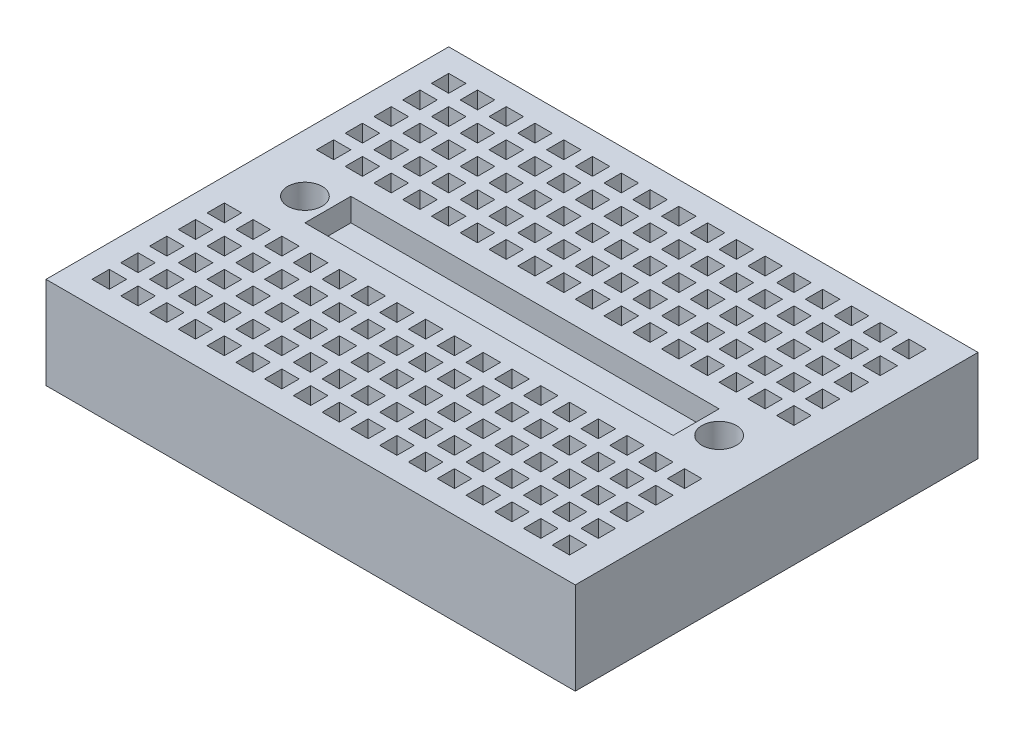
SolidWorks part; units mm, degrees
ref_plane "Front Plane" through (0, 0, 0) normal (0, 0, 1) x (1, 0, 0)
ref_plane "Top Plane" through (0, 0, 0) normal (0, 1, 0) x (1, 0, 0)
ref_plane "Right Plane" through (0, 0, 0) normal (1, 0, 0) x (0, 0, -1)
sketch "Sketch1" plane through (0, 0, 0) normal (0, 1, 0) x (1, 0, 0)
  line L1 (23, -17.5) -> (-23, -17.5)
  line L2 (23, -17.5) -> (23, 17.5)
  line L3 (23, 17.5) -> (-23, 17.5)
  line L4 (-23, -17.5) -> (-23, 17.5)
  line L5 (23, -17.5) -> (-23, 17.5) construction
  line L6 (23, 17.5) -> (-23, -17.5) construction
  circle A0 centre (18, 0) radius 1.5
  circle A1 centre (-18, 0) radius 1.5
  point P0 (0, 0)
  point P11 (-18, 0)
  dimension "D3" = 3
  dimension "D4" = 3
  dimension "D1" = 46
  dimension "D2" = 35
  dimension "D5" = 5
  dimension "D6" = 5
extrude "Boss-Extrude1" add sketch "Sketch1" along normal blind 8
sketch "Sketch3" plane through (0, 8, 0) normal (0, 1, 0) x (1, 0, 0)
  line L0 (23, 17.5) -> (-23, 17.5) construction
  line L1 (-21, 15.5) -> (-19.5, 15.5)
  line L2 (-21, 15.5) -> (-21, 14)
  line L3 (-21, 14) -> (-19.5, 14)
  line L4 (-19.5, 15.5) -> (-19.5, 14)
  line L5 (-21, 15.5) -> (-19.5, 14) construction
  line L6 (-21, 14) -> (-19.5, 15.5) construction
  line L7 (-23, 17.5) -> (-23, -17.5) construction
  line L8 (-18.5, 15.5) -> (-17, 15.5)
  line L9 (-18.5, 15.5) -> (-18.5, 14)
  line L10 (-17, 15.5) -> (-17, 14)
  line L11 (-18.5, 14) -> (-17, 14)
  line L12 (-16, 15.5) -> (-14.5, 15.5)
  line L13 (-16, 15.5) -> (-16, 14)
  line L14 (-14.5, 15.5) -> (-14.5, 14)
  line L15 (-16, 14) -> (-14.5, 14)
  line L16 (-13.5, 15.5) -> (-12, 15.5)
  line L17 (-13.5, 15.5) -> (-13.5, 14)
  line L18 (-12, 15.5) -> (-12, 14)
  line L19 (-13.5, 14) -> (-12, 14)
  line L20 (-11, 15.5) -> (-9.5, 15.5)
  line L21 (-11, 15.5) -> (-11, 14)
  line L22 (-9.5, 15.5) -> (-9.5, 14)
  line L23 (-11, 14) -> (-9.5, 14)
  line L24 (-8.5, 15.5) -> (-7, 15.5)
  line L25 (-8.5, 15.5) -> (-8.5, 14)
  line L26 (-7, 15.5) -> (-7, 14)
  line L27 (-8.5, 14) -> (-7, 14)
  line L28 (-6, 15.5) -> (-4.5, 15.5)
  line L29 (-6, 15.5) -> (-6, 14)
  line L30 (-4.5, 15.5) -> (-4.5, 14)
  line L31 (-6, 14) -> (-4.5, 14)
  line L32 (-3.5, 15.5) -> (-2, 15.5)
  line L33 (-3.5, 15.5) -> (-3.5, 14)
  line L34 (-2, 15.5) -> (-2, 14)
  line L35 (-3.5, 14) -> (-2, 14)
  line L36 (-1, 15.5) -> (0.5, 15.5)
  line L37 (-1, 15.5) -> (-1, 14)
  line L38 (0.5, 15.5) -> (0.5, 14)
  line L39 (-1, 14) -> (0.5, 14)
  line L40 (1.5, 15.5) -> (3, 15.5)
  line L41 (1.5, 15.5) -> (1.5, 14)
  line L42 (3, 15.5) -> (3, 14)
  line L43 (1.5, 14) -> (3, 14)
  line L44 (4, 15.5) -> (5.5, 15.5)
  line L45 (4, 15.5) -> (4, 14)
  line L46 (5.5, 15.5) -> (5.5, 14)
  line L47 (4, 14) -> (5.5, 14)
  line L48 (6.5, 15.5) -> (8, 15.5)
  line L49 (6.5, 15.5) -> (6.5, 14)
  line L50 (8, 15.5) -> (8, 14)
  line L51 (6.5, 14) -> (8, 14)
  line L52 (9, 15.5) -> (10.5, 15.5)
  line L53 (9, 15.5) -> (9, 14)
  line L54 (10.5, 15.5) -> (10.5, 14)
  line L55 (9, 14) -> (10.5, 14)
  line L56 (11.5, 15.5) -> (13, 15.5)
  line L57 (11.5, 15.5) -> (11.5, 14)
  line L58 (13, 15.5) -> (13, 14)
  line L59 (11.5, 14) -> (13, 14)
  line L60 (14, 15.5) -> (15.5, 15.5)
  line L61 (14, 15.5) -> (14, 14)
  line L62 (15.5, 15.5) -> (15.5, 14)
  line L63 (14, 14) -> (15.5, 14)
  line L64 (16.5, 15.5) -> (18, 15.5)
  line L65 (16.5, 15.5) -> (16.5, 14)
  line L66 (18, 15.5) -> (18, 14)
  line L67 (16.5, 14) -> (18, 14)
  line L68 (19, 15.5) -> (20.5, 15.5)
  line L69 (19, 15.5) -> (19, 14)
  line L70 (20.5, 15.5) -> (20.5, 14)
  line L71 (19, 14) -> (20.5, 14)
  line L72 (-18.5, 13) -> (-17, 13)
  line L73 (-18.5, 13) -> (-18.5, 11.5)
  line L74 (-17, 13) -> (-17, 11.5)
  line L75 (-18.5, 11.5) -> (-17, 11.5)
  line L76 (-16, 13) -> (-14.5, 13)
  line L77 (-16, 13) -> (-16, 11.5)
  line L78 (-14.5, 13) -> (-14.5, 11.5)
  line L79 (-16, 11.5) -> (-14.5, 11.5)
  line L80 (-13.5, 13) -> (-12, 13)
  line L81 (-13.5, 13) -> (-13.5, 11.5)
  line L82 (-12, 13) -> (-12, 11.5)
  line L83 (-13.5, 11.5) -> (-12, 11.5)
  line L84 (-11, 13) -> (-9.5, 13)
  line L85 (-11, 13) -> (-11, 11.5)
  line L86 (-9.5, 13) -> (-9.5, 11.5)
  line L87 (-11, 11.5) -> (-9.5, 11.5)
  line L88 (-8.5, 13) -> (-7, 13)
  line L89 (-8.5, 13) -> (-8.5, 11.5)
  line L90 (-7, 13) -> (-7, 11.5)
  line L91 (-8.5, 11.5) -> (-7, 11.5)
  line L92 (-6, 13) -> (-4.5, 13)
  line L93 (-6, 13) -> (-6, 11.5)
  line L94 (-4.5, 13) -> (-4.5, 11.5)
  line L95 (-6, 11.5) -> (-4.5, 11.5)
  line L96 (-3.5, 13) -> (-2, 13)
  line L97 (-3.5, 13) -> (-3.5, 11.5)
  line L98 (-2, 13) -> (-2, 11.5)
  line L99 (-3.5, 11.5) -> (-2, 11.5)
  line L100 (-1, 13) -> (0.5, 13)
  line L101 (-1, 13) -> (-1, 11.5)
  line L102 (0.5, 13) -> (0.5, 11.5)
  line L103 (-1, 11.5) -> (0.5, 11.5)
  line L104 (1.5, 13) -> (3, 13)
  line L105 (1.5, 13) -> (1.5, 11.5)
  line L106 (3, 13) -> (3, 11.5)
  line L107 (1.5, 11.5) -> (3, 11.5)
  line L108 (4, 13) -> (5.5, 13)
  line L109 (4, 13) -> (4, 11.5)
  line L110 (5.5, 13) -> (5.5, 11.5)
  line L111 (4, 11.5) -> (5.5, 11.5)
  line L112 (6.5, 13) -> (8, 13)
  line L113 (6.5, 13) -> (6.5, 11.5)
  line L114 (8, 13) -> (8, 11.5)
  line L115 (6.5, 11.5) -> (8, 11.5)
  line L116 (9, 13) -> (10.5, 13)
  line L117 (9, 13) -> (9, 11.5)
  line L118 (10.5, 13) -> (10.5, 11.5)
  line L119 (9, 11.5) -> (10.5, 11.5)
  line L120 (11.5, 13) -> (13, 13)
  line L121 (11.5, 13) -> (11.5, 11.5)
  line L122 (13, 13) -> (13, 11.5)
  line L123 (11.5, 11.5) -> (13, 11.5)
  line L124 (14, 13) -> (15.5, 13)
  line L125 (14, 13) -> (14, 11.5)
  line L126 (15.5, 13) -> (15.5, 11.5)
  line L127 (14, 11.5) -> (15.5, 11.5)
  line L128 (16.5, 13) -> (18, 13)
  line L129 (16.5, 13) -> (16.5, 11.5)
  line L130 (18, 13) -> (18, 11.5)
  line L131 (16.5, 11.5) -> (18, 11.5)
  line L132 (19, 13) -> (20.5, 13)
  line L133 (19, 13) -> (19, 11.5)
  line L134 (20.5, 13) -> (20.5, 11.5)
  line L135 (19, 11.5) -> (20.5, 11.5)
  line L136 (-18.5, 10.5) -> (-17, 10.5)
  line L137 (-18.5, 10.5) -> (-18.5, 9)
  line L138 (-17, 10.5) -> (-17, 9)
  line L139 (-18.5, 9) -> (-17, 9)
  line L140 (-16, 10.5) -> (-14.5, 10.5)
  line L141 (-16, 10.5) -> (-16, 9)
  line L142 (-14.5, 10.5) -> (-14.5, 9)
  line L143 (-16, 9) -> (-14.5, 9)
  line L144 (-13.5, 10.5) -> (-12, 10.5)
  line L145 (-13.5, 10.5) -> (-13.5, 9)
  line L146 (-12, 10.5) -> (-12, 9)
  line L147 (-13.5, 9) -> (-12, 9)
  line L148 (-11, 10.5) -> (-9.5, 10.5)
  line L149 (-11, 10.5) -> (-11, 9)
  line L150 (-9.5, 10.5) -> (-9.5, 9)
  line L151 (-11, 9) -> (-9.5, 9)
  line L152 (-8.5, 10.5) -> (-7, 10.5)
  line L153 (-8.5, 10.5) -> (-8.5, 9)
  line L154 (-7, 10.5) -> (-7, 9)
  line L155 (-8.5, 9) -> (-7, 9)
  line L156 (-6, 10.5) -> (-4.5, 10.5)
  line L157 (-6, 10.5) -> (-6, 9)
  line L158 (-4.5, 10.5) -> (-4.5, 9)
  line L159 (-6, 9) -> (-4.5, 9)
  line L160 (-3.5, 10.5) -> (-2, 10.5)
  line L161 (-3.5, 10.5) -> (-3.5, 9)
  line L162 (-2, 10.5) -> (-2, 9)
  line L163 (-3.5, 9) -> (-2, 9)
  line L164 (-1, 10.5) -> (0.5, 10.5)
  line L165 (-1, 10.5) -> (-1, 9)
  line L166 (0.5, 10.5) -> (0.5, 9)
  line L167 (-1, 9) -> (0.5, 9)
  line L168 (1.5, 10.5) -> (3, 10.5)
  line L169 (1.5, 10.5) -> (1.5, 9)
  line L170 (3, 10.5) -> (3, 9)
  line L171 (1.5, 9) -> (3, 9)
  line L172 (4, 10.5) -> (5.5, 10.5)
  line L173 (4, 10.5) -> (4, 9)
  line L174 (5.5, 10.5) -> (5.5, 9)
  line L175 (4, 9) -> (5.5, 9)
  line L176 (6.5, 10.5) -> (8, 10.5)
  line L177 (6.5, 10.5) -> (6.5, 9)
  line L178 (8, 10.5) -> (8, 9)
  line L179 (6.5, 9) -> (8, 9)
  line L180 (9, 10.5) -> (10.5, 10.5)
  line L181 (9, 10.5) -> (9, 9)
  line L182 (10.5, 10.5) -> (10.5, 9)
  line L183 (9, 9) -> (10.5, 9)
  line L184 (11.5, 10.5) -> (13, 10.5)
  line L185 (11.5, 10.5) -> (11.5, 9)
  line L186 (13, 10.5) -> (13, 9)
  line L187 (11.5, 9) -> (13, 9)
  line L188 (14, 10.5) -> (15.5, 10.5)
  line L189 (14, 10.5) -> (14, 9)
  line L190 (15.5, 10.5) -> (15.5, 9)
  line L191 (14, 9) -> (15.5, 9)
  line L192 (16.5, 10.5) -> (18, 10.5)
  line L193 (16.5, 10.5) -> (16.5, 9)
  line L194 (18, 10.5) -> (18, 9)
  line L195 (16.5, 9) -> (18, 9)
  line L196 (19, 10.5) -> (20.5, 10.5)
  line L197 (19, 10.5) -> (19, 9)
  line L198 (20.5, 10.5) -> (20.5, 9)
  line L199 (19, 9) -> (20.5, 9)
  line L200 (-18.5, 8) -> (-17, 8)
  line L201 (-18.5, 8) -> (-18.5, 6.5)
  line L202 (-17, 8) -> (-17, 6.5)
  line L203 (-18.5, 6.5) -> (-17, 6.5)
  line L204 (-16, 8) -> (-14.5, 8)
  line L205 (-16, 8) -> (-16, 6.5)
  line L206 (-14.5, 8) -> (-14.5, 6.5)
  line L207 (-16, 6.5) -> (-14.5, 6.5)
  line L208 (-13.5, 8) -> (-12, 8)
  line L209 (-13.5, 8) -> (-13.5, 6.5)
  line L210 (-12, 8) -> (-12, 6.5)
  line L211 (-13.5, 6.5) -> (-12, 6.5)
  line L212 (-11, 8) -> (-9.5, 8)
  line L213 (-11, 8) -> (-11, 6.5)
  line L214 (-9.5, 8) -> (-9.5, 6.5)
  line L215 (-11, 6.5) -> (-9.5, 6.5)
  line L216 (-8.5, 8) -> (-7, 8)
  line L217 (-8.5, 8) -> (-8.5, 6.5)
  line L218 (-7, 8) -> (-7, 6.5)
  line L219 (-8.5, 6.5) -> (-7, 6.5)
  line L220 (-6, 8) -> (-4.5, 8)
  line L221 (-6, 8) -> (-6, 6.5)
  line L222 (-4.5, 8) -> (-4.5, 6.5)
  line L223 (-6, 6.5) -> (-4.5, 6.5)
  line L224 (-3.5, 8) -> (-2, 8)
  line L225 (-3.5, 8) -> (-3.5, 6.5)
  line L226 (-2, 8) -> (-2, 6.5)
  line L227 (-3.5, 6.5) -> (-2, 6.5)
  line L228 (-1, 8) -> (0.5, 8)
  line L229 (-1, 8) -> (-1, 6.5)
  line L230 (0.5, 8) -> (0.5, 6.5)
  line L231 (-1, 6.5) -> (0.5, 6.5)
  line L232 (1.5, 8) -> (3, 8)
  line L233 (1.5, 8) -> (1.5, 6.5)
  line L234 (3, 8) -> (3, 6.5)
  line L235 (1.5, 6.5) -> (3, 6.5)
  line L236 (4, 8) -> (5.5, 8)
  line L237 (4, 8) -> (4, 6.5)
  line L238 (5.5, 8) -> (5.5, 6.5)
  line L239 (4, 6.5) -> (5.5, 6.5)
  line L240 (6.5, 8) -> (8, 8)
  line L241 (6.5, 8) -> (6.5, 6.5)
  line L242 (8, 8) -> (8, 6.5)
  line L243 (6.5, 6.5) -> (8, 6.5)
  line L244 (9, 8) -> (10.5, 8)
  line L245 (9, 8) -> (9, 6.5)
  line L246 (10.5, 8) -> (10.5, 6.5)
  line L247 (9, 6.5) -> (10.5, 6.5)
  line L248 (11.5, 8) -> (13, 8)
  line L249 (11.5, 8) -> (11.5, 6.5)
  line L250 (13, 8) -> (13, 6.5)
  line L251 (11.5, 6.5) -> (13, 6.5)
  line L252 (14, 8) -> (15.5, 8)
  line L253 (14, 8) -> (14, 6.5)
  line L254 (15.5, 8) -> (15.5, 6.5)
  line L255 (14, 6.5) -> (15.5, 6.5)
  line L256 (16.5, 8) -> (18, 8)
  line L257 (16.5, 8) -> (16.5, 6.5)
  line L258 (18, 8) -> (18, 6.5)
  line L259 (16.5, 6.5) -> (18, 6.5)
  line L260 (19, 8) -> (20.5, 8)
  line L261 (19, 8) -> (19, 6.5)
  line L262 (20.5, 8) -> (20.5, 6.5)
  line L263 (19, 6.5) -> (20.5, 6.5)
  line L264 (-18.5, 5.5) -> (-17, 5.5)
  line L265 (-18.5, 5.5) -> (-18.5, 4)
  line L266 (-17, 5.5) -> (-17, 4)
  line L267 (-18.5, 4) -> (-17, 4)
  line L268 (-16, 5.5) -> (-14.5, 5.5)
  line L269 (-16, 5.5) -> (-16, 4)
  line L270 (-14.5, 5.5) -> (-14.5, 4)
  line L271 (-16, 4) -> (-14.5, 4)
  line L272 (-13.5, 5.5) -> (-12, 5.5)
  line L273 (-13.5, 5.5) -> (-13.5, 4)
  line L274 (-12, 5.5) -> (-12, 4)
  line L275 (-13.5, 4) -> (-12, 4)
  line L276 (-11, 5.5) -> (-9.5, 5.5)
  line L277 (-11, 5.5) -> (-11, 4)
  line L278 (-9.5, 5.5) -> (-9.5, 4)
  line L279 (-11, 4) -> (-9.5, 4)
  line L280 (-8.5, 5.5) -> (-7, 5.5)
  line L281 (-8.5, 5.5) -> (-8.5, 4)
  line L282 (-7, 5.5) -> (-7, 4)
  line L283 (-8.5, 4) -> (-7, 4)
  line L284 (-6, 5.5) -> (-4.5, 5.5)
  line L285 (-6, 5.5) -> (-6, 4)
  line L286 (-4.5, 5.5) -> (-4.5, 4)
  line L287 (-6, 4) -> (-4.5, 4)
  line L288 (-3.5, 5.5) -> (-2, 5.5)
  line L289 (-3.5, 5.5) -> (-3.5, 4)
  line L290 (-2, 5.5) -> (-2, 4)
  line L291 (-3.5, 4) -> (-2, 4)
  line L292 (-1, 5.5) -> (0.5, 5.5)
  line L293 (-1, 5.5) -> (-1, 4)
  line L294 (0.5, 5.5) -> (0.5, 4)
  line L295 (-1, 4) -> (0.5, 4)
  line L296 (1.5, 5.5) -> (3, 5.5)
  line L297 (1.5, 5.5) -> (1.5, 4)
  line L298 (3, 5.5) -> (3, 4)
  line L299 (1.5, 4) -> (3, 4)
  line L300 (4, 5.5) -> (5.5, 5.5)
  line L301 (4, 5.5) -> (4, 4)
  line L302 (5.5, 5.5) -> (5.5, 4)
  line L303 (4, 4) -> (5.5, 4)
  line L304 (6.5, 5.5) -> (8, 5.5)
  line L305 (6.5, 5.5) -> (6.5, 4)
  line L306 (8, 5.5) -> (8, 4)
  line L307 (6.5, 4) -> (8, 4)
  line L308 (9, 5.5) -> (10.5, 5.5)
  line L309 (9, 5.5) -> (9, 4)
  line L310 (10.5, 5.5) -> (10.5, 4)
  line L311 (9, 4) -> (10.5, 4)
  line L312 (11.5, 5.5) -> (13, 5.5)
  line L313 (11.5, 5.5) -> (11.5, 4)
  line L314 (13, 5.5) -> (13, 4)
  line L315 (11.5, 4) -> (13, 4)
  line L316 (14, 5.5) -> (15.5, 5.5)
  line L317 (14, 5.5) -> (14, 4)
  line L318 (15.5, 5.5) -> (15.5, 4)
  line L319 (14, 4) -> (15.5, 4)
  line L320 (16.5, 5.5) -> (18, 5.5)
  line L321 (16.5, 5.5) -> (16.5, 4)
  line L322 (18, 5.5) -> (18, 4)
  line L323 (16.5, 4) -> (18, 4)
  line L324 (19, 5.5) -> (20.5, 5.5)
  line L325 (19, 5.5) -> (19, 4)
  line L326 (20.5, 5.5) -> (20.5, 4)
  line L327 (19, 4) -> (20.5, 4)
  line L328 (-21, 13) -> (-19.5, 13)
  line L329 (-21, 13) -> (-21, 11.5)
  line L330 (-19.5, 13) -> (-19.5, 11.5)
  line L331 (-21, 11.5) -> (-19.5, 11.5)
  line L332 (-21, 10.5) -> (-19.5, 10.5)
  line L333 (-21, 10.5) -> (-21, 9)
  line L334 (-19.5, 10.5) -> (-19.5, 9)
  line L335 (-21, 9) -> (-19.5, 9)
  line L336 (-21, 8) -> (-19.5, 8)
  line L337 (-21, 8) -> (-21, 6.5)
  line L338 (-19.5, 8) -> (-19.5, 6.5)
  line L339 (-21, 6.5) -> (-19.5, 6.5)
  line L340 (-21, 5.5) -> (-19.5, 5.5)
  line L341 (-21, 5.5) -> (-21, 4)
  line L342 (-19.5, 5.5) -> (-19.5, 4)
  line L343 (-21, 4) -> (-19.5, 4)
  line L344 (-23, 0) -> (23, 0) construction
  line L345 (23, -17.5) -> (23, 17.5) construction
  line L346 (-21, -14) -> (-19.5, -15.5) construction
  line L347 (-21, -15.5) -> (-19.5, -14) construction
  line L348 (-21, -4) -> (-19.5, -4)
  line L349 (-19.5, -5.5) -> (-19.5, -4)
  line L350 (-21, -5.5) -> (-21, -4)
  line L351 (-21, -5.5) -> (-19.5, -5.5)
  line L352 (-21, -6.5) -> (-19.5, -6.5)
  line L353 (-19.5, -8) -> (-19.5, -6.5)
  line L354 (-21, -8) -> (-21, -6.5)
  line L355 (-21, -8) -> (-19.5, -8)
  line L356 (-21, -9) -> (-19.5, -9)
  line L357 (-19.5, -10.5) -> (-19.5, -9)
  line L358 (-21, -10.5) -> (-21, -9)
  line L359 (-21, -10.5) -> (-19.5, -10.5)
  line L360 (-21, -11.5) -> (-19.5, -11.5)
  line L361 (-19.5, -13) -> (-19.5, -11.5)
  line L362 (-21, -13) -> (-21, -11.5)
  line L363 (-21, -13) -> (-19.5, -13)
  line L364 (19, -4) -> (20.5, -4)
  line L365 (20.5, -5.5) -> (20.5, -4)
  line L366 (19, -5.5) -> (19, -4)
  line L367 (19, -5.5) -> (20.5, -5.5)
  line L368 (16.5, -4) -> (18, -4)
  line L369 (18, -5.5) -> (18, -4)
  line L370 (16.5, -5.5) -> (16.5, -4)
  line L371 (16.5, -5.5) -> (18, -5.5)
  line L372 (14, -4) -> (15.5, -4)
  line L373 (15.5, -5.5) -> (15.5, -4)
  line L374 (14, -5.5) -> (14, -4)
  line L375 (14, -5.5) -> (15.5, -5.5)
  line L376 (11.5, -4) -> (13, -4)
  line L377 (13, -5.5) -> (13, -4)
  line L378 (11.5, -5.5) -> (11.5, -4)
  line L379 (11.5, -5.5) -> (13, -5.5)
  line L380 (9, -4) -> (10.5, -4)
  line L381 (10.5, -5.5) -> (10.5, -4)
  line L382 (9, -5.5) -> (9, -4)
  line L383 (9, -5.5) -> (10.5, -5.5)
  line L384 (6.5, -4) -> (8, -4)
  line L385 (8, -5.5) -> (8, -4)
  line L386 (6.5, -5.5) -> (6.5, -4)
  line L387 (6.5, -5.5) -> (8, -5.5)
  line L388 (4, -4) -> (5.5, -4)
  line L389 (5.5, -5.5) -> (5.5, -4)
  line L390 (4, -5.5) -> (4, -4)
  line L391 (4, -5.5) -> (5.5, -5.5)
  line L392 (1.5, -4) -> (3, -4)
  line L393 (3, -5.5) -> (3, -4)
  line L394 (1.5, -5.5) -> (1.5, -4)
  line L395 (1.5, -5.5) -> (3, -5.5)
  line L396 (-1, -4) -> (0.5, -4)
  line L397 (0.5, -5.5) -> (0.5, -4)
  line L398 (-1, -5.5) -> (-1, -4)
  line L399 (-1, -5.5) -> (0.5, -5.5)
  line L400 (-3.5, -4) -> (-2, -4)
  line L401 (-2, -5.5) -> (-2, -4)
  line L402 (-3.5, -5.5) -> (-3.5, -4)
  line L403 (-3.5, -5.5) -> (-2, -5.5)
  line L404 (-6, -4) -> (-4.5, -4)
  line L405 (-4.5, -5.5) -> (-4.5, -4)
  line L406 (-6, -5.5) -> (-6, -4)
  line L407 (-6, -5.5) -> (-4.5, -5.5)
  line L408 (-8.5, -4) -> (-7, -4)
  line L409 (-7, -5.5) -> (-7, -4)
  line L410 (-8.5, -5.5) -> (-8.5, -4)
  line L411 (-8.5, -5.5) -> (-7, -5.5)
  line L412 (-11, -4) -> (-9.5, -4)
  line L413 (-9.5, -5.5) -> (-9.5, -4)
  line L414 (-11, -5.5) -> (-11, -4)
  line L415 (-11, -5.5) -> (-9.5, -5.5)
  line L416 (-13.5, -4) -> (-12, -4)
  line L417 (-12, -5.5) -> (-12, -4)
  line L418 (-13.5, -5.5) -> (-13.5, -4)
  line L419 (-13.5, -5.5) -> (-12, -5.5)
  line L420 (-16, -4) -> (-14.5, -4)
  line L421 (-14.5, -5.5) -> (-14.5, -4)
  line L422 (-16, -5.5) -> (-16, -4)
  line L423 (-16, -5.5) -> (-14.5, -5.5)
  line L424 (-18.5, -4) -> (-17, -4)
  line L425 (-17, -5.5) -> (-17, -4)
  line L426 (-18.5, -5.5) -> (-18.5, -4)
  line L427 (-18.5, -5.5) -> (-17, -5.5)
  line L428 (19, -6.5) -> (20.5, -6.5)
  line L429 (20.5, -8) -> (20.5, -6.5)
  line L430 (19, -8) -> (19, -6.5)
  line L431 (19, -8) -> (20.5, -8)
  line L432 (16.5, -6.5) -> (18, -6.5)
  line L433 (18, -8) -> (18, -6.5)
  line L434 (16.5, -8) -> (16.5, -6.5)
  line L435 (16.5, -8) -> (18, -8)
  line L436 (14, -6.5) -> (15.5, -6.5)
  line L437 (15.5, -8) -> (15.5, -6.5)
  line L438 (14, -8) -> (14, -6.5)
  line L439 (14, -8) -> (15.5, -8)
  line L440 (11.5, -6.5) -> (13, -6.5)
  line L441 (13, -8) -> (13, -6.5)
  line L442 (11.5, -8) -> (11.5, -6.5)
  line L443 (11.5, -8) -> (13, -8)
  line L444 (9, -6.5) -> (10.5, -6.5)
  line L445 (10.5, -8) -> (10.5, -6.5)
  line L446 (9, -8) -> (9, -6.5)
  line L447 (9, -8) -> (10.5, -8)
  line L448 (6.5, -6.5) -> (8, -6.5)
  line L449 (8, -8) -> (8, -6.5)
  line L450 (6.5, -8) -> (6.5, -6.5)
  line L451 (6.5, -8) -> (8, -8)
  line L452 (4, -6.5) -> (5.5, -6.5)
  line L453 (5.5, -8) -> (5.5, -6.5)
  line L454 (4, -8) -> (4, -6.5)
  line L455 (4, -8) -> (5.5, -8)
  line L456 (1.5, -6.5) -> (3, -6.5)
  line L457 (3, -8) -> (3, -6.5)
  line L458 (1.5, -8) -> (1.5, -6.5)
  line L459 (1.5, -8) -> (3, -8)
  line L460 (-1, -6.5) -> (0.5, -6.5)
  line L461 (0.5, -8) -> (0.5, -6.5)
  line L462 (-1, -8) -> (-1, -6.5)
  line L463 (-1, -8) -> (0.5, -8)
  line L464 (-3.5, -6.5) -> (-2, -6.5)
  line L465 (-2, -8) -> (-2, -6.5)
  line L466 (-3.5, -8) -> (-3.5, -6.5)
  line L467 (-3.5, -8) -> (-2, -8)
  line L468 (-6, -6.5) -> (-4.5, -6.5)
  line L469 (-4.5, -8) -> (-4.5, -6.5)
  line L470 (-6, -8) -> (-6, -6.5)
  line L471 (-6, -8) -> (-4.5, -8)
  line L472 (-8.5, -6.5) -> (-7, -6.5)
  line L473 (-7, -8) -> (-7, -6.5)
  line L474 (-8.5, -8) -> (-8.5, -6.5)
  line L475 (-8.5, -8) -> (-7, -8)
  line L476 (-11, -6.5) -> (-9.5, -6.5)
  line L477 (-9.5, -8) -> (-9.5, -6.5)
  line L478 (-11, -8) -> (-11, -6.5)
  line L479 (-11, -8) -> (-9.5, -8)
  line L480 (-13.5, -6.5) -> (-12, -6.5)
  line L481 (-12, -8) -> (-12, -6.5)
  line L482 (-13.5, -8) -> (-13.5, -6.5)
  line L483 (-13.5, -8) -> (-12, -8)
  line L484 (-16, -6.5) -> (-14.5, -6.5)
  line L485 (-14.5, -8) -> (-14.5, -6.5)
  line L486 (-16, -8) -> (-16, -6.5)
  line L487 (-16, -8) -> (-14.5, -8)
  line L488 (-18.5, -6.5) -> (-17, -6.5)
  line L489 (-17, -8) -> (-17, -6.5)
  line L490 (-18.5, -8) -> (-18.5, -6.5)
  line L491 (-18.5, -8) -> (-17, -8)
  line L492 (19, -9) -> (20.5, -9)
  line L493 (20.5, -10.5) -> (20.5, -9)
  line L494 (19, -10.5) -> (19, -9)
  line L495 (19, -10.5) -> (20.5, -10.5)
  line L496 (16.5, -9) -> (18, -9)
  line L497 (18, -10.5) -> (18, -9)
  line L498 (16.5, -10.5) -> (16.5, -9)
  line L499 (16.5, -10.5) -> (18, -10.5)
  line L500 (14, -9) -> (15.5, -9)
  line L501 (15.5, -10.5) -> (15.5, -9)
  line L502 (14, -10.5) -> (14, -9)
  line L503 (14, -10.5) -> (15.5, -10.5)
  line L504 (11.5, -9) -> (13, -9)
  line L505 (13, -10.5) -> (13, -9)
  line L506 (11.5, -10.5) -> (11.5, -9)
  line L507 (11.5, -10.5) -> (13, -10.5)
  line L508 (9, -9) -> (10.5, -9)
  line L509 (10.5, -10.5) -> (10.5, -9)
  line L510 (9, -10.5) -> (9, -9)
  line L511 (9, -10.5) -> (10.5, -10.5)
  line L512 (6.5, -9) -> (8, -9)
  line L513 (8, -10.5) -> (8, -9)
  line L514 (6.5, -10.5) -> (6.5, -9)
  line L515 (6.5, -10.5) -> (8, -10.5)
  line L516 (4, -9) -> (5.5, -9)
  line L517 (5.5, -10.5) -> (5.5, -9)
  line L518 (4, -10.5) -> (4, -9)
  line L519 (4, -10.5) -> (5.5, -10.5)
  line L520 (1.5, -9) -> (3, -9)
  line L521 (3, -10.5) -> (3, -9)
  line L522 (1.5, -10.5) -> (1.5, -9)
  line L523 (1.5, -10.5) -> (3, -10.5)
  line L524 (-1, -9) -> (0.5, -9)
  line L525 (0.5, -10.5) -> (0.5, -9)
  line L526 (-1, -10.5) -> (-1, -9)
  line L527 (-1, -10.5) -> (0.5, -10.5)
  line L528 (-3.5, -9) -> (-2, -9)
  line L529 (-2, -10.5) -> (-2, -9)
  line L530 (-3.5, -10.5) -> (-3.5, -9)
  line L531 (-3.5, -10.5) -> (-2, -10.5)
  line L532 (-6, -9) -> (-4.5, -9)
  line L533 (-4.5, -10.5) -> (-4.5, -9)
  line L534 (-6, -10.5) -> (-6, -9)
  line L535 (-6, -10.5) -> (-4.5, -10.5)
  line L536 (-8.5, -9) -> (-7, -9)
  line L537 (-7, -10.5) -> (-7, -9)
  line L538 (-8.5, -10.5) -> (-8.5, -9)
  line L539 (-8.5, -10.5) -> (-7, -10.5)
  line L540 (-11, -9) -> (-9.5, -9)
  line L541 (-9.5, -10.5) -> (-9.5, -9)
  line L542 (-11, -10.5) -> (-11, -9)
  line L543 (-11, -10.5) -> (-9.5, -10.5)
  line L544 (-13.5, -9) -> (-12, -9)
  line L545 (-12, -10.5) -> (-12, -9)
  line L546 (-13.5, -10.5) -> (-13.5, -9)
  line L547 (-13.5, -10.5) -> (-12, -10.5)
  line L548 (-16, -9) -> (-14.5, -9)
  line L549 (-14.5, -10.5) -> (-14.5, -9)
  line L550 (-16, -10.5) -> (-16, -9)
  line L551 (-16, -10.5) -> (-14.5, -10.5)
  line L552 (-18.5, -9) -> (-17, -9)
  line L553 (-17, -10.5) -> (-17, -9)
  line L554 (-18.5, -10.5) -> (-18.5, -9)
  line L555 (-18.5, -10.5) -> (-17, -10.5)
  line L556 (19, -11.5) -> (20.5, -11.5)
  line L557 (20.5, -13) -> (20.5, -11.5)
  line L558 (19, -13) -> (19, -11.5)
  line L559 (19, -13) -> (20.5, -13)
  line L560 (16.5, -11.5) -> (18, -11.5)
  line L561 (18, -13) -> (18, -11.5)
  line L562 (16.5, -13) -> (16.5, -11.5)
  line L563 (16.5, -13) -> (18, -13)
  line L564 (14, -11.5) -> (15.5, -11.5)
  line L565 (15.5, -13) -> (15.5, -11.5)
  line L566 (14, -13) -> (14, -11.5)
  line L567 (14, -13) -> (15.5, -13)
  line L568 (11.5, -11.5) -> (13, -11.5)
  line L569 (13, -13) -> (13, -11.5)
  line L570 (11.5, -13) -> (11.5, -11.5)
  line L571 (11.5, -13) -> (13, -13)
  line L572 (9, -11.5) -> (10.5, -11.5)
  line L573 (10.5, -13) -> (10.5, -11.5)
  line L574 (9, -13) -> (9, -11.5)
  line L575 (9, -13) -> (10.5, -13)
  line L576 (6.5, -11.5) -> (8, -11.5)
  line L577 (8, -13) -> (8, -11.5)
  line L578 (6.5, -13) -> (6.5, -11.5)
  line L579 (6.5, -13) -> (8, -13)
  line L580 (4, -11.5) -> (5.5, -11.5)
  line L581 (5.5, -13) -> (5.5, -11.5)
  line L582 (4, -13) -> (4, -11.5)
  line L583 (4, -13) -> (5.5, -13)
  line L584 (1.5, -11.5) -> (3, -11.5)
  line L585 (3, -13) -> (3, -11.5)
  line L586 (1.5, -13) -> (1.5, -11.5)
  line L587 (1.5, -13) -> (3, -13)
  line L588 (-1, -11.5) -> (0.5, -11.5)
  line L589 (0.5, -13) -> (0.5, -11.5)
  line L590 (-1, -13) -> (-1, -11.5)
  line L591 (-1, -13) -> (0.5, -13)
  line L592 (-3.5, -11.5) -> (-2, -11.5)
  line L593 (-2, -13) -> (-2, -11.5)
  line L594 (-3.5, -13) -> (-3.5, -11.5)
  line L595 (-3.5, -13) -> (-2, -13)
  line L596 (-6, -11.5) -> (-4.5, -11.5)
  line L597 (-4.5, -13) -> (-4.5, -11.5)
  line L598 (-6, -13) -> (-6, -11.5)
  line L599 (-6, -13) -> (-4.5, -13)
  line L600 (-8.5, -11.5) -> (-7, -11.5)
  line L601 (-7, -13) -> (-7, -11.5)
  line L602 (-8.5, -13) -> (-8.5, -11.5)
  line L603 (-8.5, -13) -> (-7, -13)
  line L604 (-11, -11.5) -> (-9.5, -11.5)
  line L605 (-9.5, -13) -> (-9.5, -11.5)
  line L606 (-11, -13) -> (-11, -11.5)
  line L607 (-11, -13) -> (-9.5, -13)
  line L608 (-13.5, -11.5) -> (-12, -11.5)
  line L609 (-12, -13) -> (-12, -11.5)
  line L610 (-13.5, -13) -> (-13.5, -11.5)
  line L611 (-13.5, -13) -> (-12, -13)
  line L612 (-16, -11.5) -> (-14.5, -11.5)
  line L613 (-14.5, -13) -> (-14.5, -11.5)
  line L614 (-16, -13) -> (-16, -11.5)
  line L615 (-16, -13) -> (-14.5, -13)
  line L616 (-18.5, -11.5) -> (-17, -11.5)
  line L617 (-17, -13) -> (-17, -11.5)
  line L618 (-18.5, -13) -> (-18.5, -11.5)
  line L619 (-18.5, -13) -> (-17, -13)
  line L620 (19, -14) -> (20.5, -14)
  line L621 (20.5, -15.5) -> (20.5, -14)
  line L622 (19, -15.5) -> (19, -14)
  line L623 (19, -15.5) -> (20.5, -15.5)
  line L624 (16.5, -14) -> (18, -14)
  line L625 (18, -15.5) -> (18, -14)
  line L626 (16.5, -15.5) -> (16.5, -14)
  line L627 (16.5, -15.5) -> (18, -15.5)
  line L628 (14, -14) -> (15.5, -14)
  line L629 (15.5, -15.5) -> (15.5, -14)
  line L630 (14, -15.5) -> (14, -14)
  line L631 (14, -15.5) -> (15.5, -15.5)
  line L632 (11.5, -14) -> (13, -14)
  line L633 (13, -15.5) -> (13, -14)
  line L634 (11.5, -15.5) -> (11.5, -14)
  line L635 (11.5, -15.5) -> (13, -15.5)
  line L636 (9, -14) -> (10.5, -14)
  line L637 (10.5, -15.5) -> (10.5, -14)
  line L638 (9, -15.5) -> (9, -14)
  line L639 (9, -15.5) -> (10.5, -15.5)
  line L640 (6.5, -14) -> (8, -14)
  line L641 (8, -15.5) -> (8, -14)
  line L642 (6.5, -15.5) -> (6.5, -14)
  line L643 (6.5, -15.5) -> (8, -15.5)
  line L644 (4, -14) -> (5.5, -14)
  line L645 (5.5, -15.5) -> (5.5, -14)
  line L646 (4, -15.5) -> (4, -14)
  line L647 (4, -15.5) -> (5.5, -15.5)
  line L648 (1.5, -14) -> (3, -14)
  line L649 (3, -15.5) -> (3, -14)
  line L650 (1.5, -15.5) -> (1.5, -14)
  line L651 (1.5, -15.5) -> (3, -15.5)
  line L652 (-1, -14) -> (0.5, -14)
  line L653 (0.5, -15.5) -> (0.5, -14)
  line L654 (-1, -15.5) -> (-1, -14)
  line L655 (-1, -15.5) -> (0.5, -15.5)
  line L656 (-3.5, -14) -> (-2, -14)
  line L657 (-2, -15.5) -> (-2, -14)
  line L658 (-3.5, -15.5) -> (-3.5, -14)
  line L659 (-3.5, -15.5) -> (-2, -15.5)
  line L660 (-6, -14) -> (-4.5, -14)
  line L661 (-4.5, -15.5) -> (-4.5, -14)
  line L662 (-6, -15.5) -> (-6, -14)
  line L663 (-6, -15.5) -> (-4.5, -15.5)
  line L664 (-8.5, -14) -> (-7, -14)
  line L665 (-7, -15.5) -> (-7, -14)
  line L666 (-8.5, -15.5) -> (-8.5, -14)
  line L667 (-8.5, -15.5) -> (-7, -15.5)
  line L668 (-11, -14) -> (-9.5, -14)
  line L669 (-9.5, -15.5) -> (-9.5, -14)
  line L670 (-11, -15.5) -> (-11, -14)
  line L671 (-11, -15.5) -> (-9.5, -15.5)
  line L672 (-13.5, -14) -> (-12, -14)
  line L673 (-12, -15.5) -> (-12, -14)
  line L674 (-13.5, -15.5) -> (-13.5, -14)
  line L675 (-13.5, -15.5) -> (-12, -15.5)
  line L676 (-16, -14) -> (-14.5, -14)
  line L677 (-14.5, -15.5) -> (-14.5, -14)
  line L678 (-16, -15.5) -> (-16, -14)
  line L679 (-16, -15.5) -> (-14.5, -15.5)
  line L680 (-18.5, -14) -> (-17, -14)
  line L681 (-17, -15.5) -> (-17, -14)
  line L682 (-18.5, -15.5) -> (-18.5, -14)
  line L683 (-18.5, -15.5) -> (-17, -15.5)
  line L684 (-19.5, -15.5) -> (-19.5, -14)
  line L685 (-21, -14) -> (-19.5, -14)
  line L686 (-21, -15.5) -> (-21, -14)
  line L687 (-21, -15.5) -> (-19.5, -15.5)
  point P0 (-20.25, 14.75)
  point P689 (-20.25, -14.75)
  dimension "D1" = 1.5
  dimension "D2" = 2
  dimension "D3" = 2
  dimension "D4" = 1.5
  dimension "D5" = 17
  dimension "D6" = 5
extrude "Cut-Extrude2" cut sketch "Sketch3" against normal blind 7
sketch "Sketch2" plane through (0, 8, 0) normal (0, 1, 0) x (1, 0, 0)
  line L1 (16, -2) -> (-16, -2)
  line L2 (16, -2) -> (16, 2)
  line L3 (16, 2) -> (-16, 2)
  line L4 (-16, -2) -> (-16, 2)
  line L5 (16, -2) -> (-16, 2) construction
  line L6 (16, 2) -> (-16, -2) construction
  circle A0 centre (-18, 0) radius 1.5 construction
  point P0 (0, 0)
  dimension "D1" = 4
  dimension "D2" = 2
extrude "Cut-Extrude1" cut sketch "Sketch2" against normal blind 2
ref_plane "Plane1" through (0, 0, 0) normal (-1, 0, 0) x (0, 0, 1)
